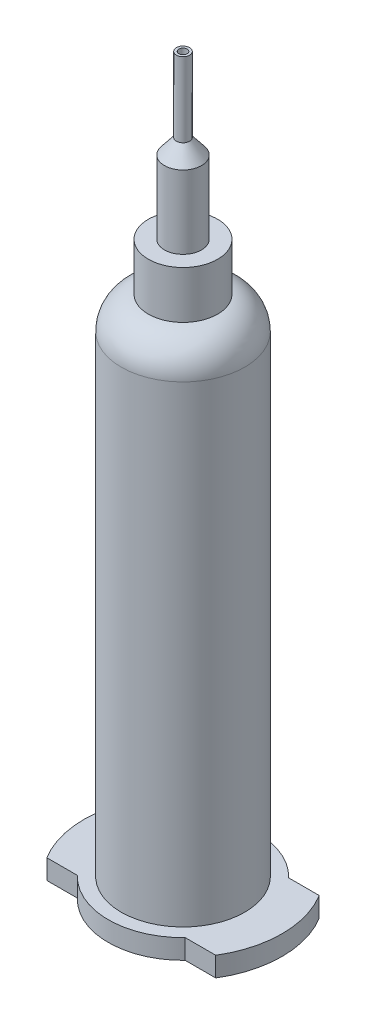
SolidWorks part; units mm, degrees
ref_plane "Front Plane" through (0, 0, 0) normal (0, 0, 1) x (1, 0, 0)
ref_plane "Top Plane" through (0, 0, 0) normal (0, 1, 0) x (1, 0, 0)
ref_plane "Right Plane" through (0, 0, 0) normal (1, 0, 0) x (0, 0, -1)
ref_axis "Axis1" through (-33.0333, 0, 0) along (1, 0, 0)
ref_axis "Axis2" through (0, 24.5224, 0) along (0, -1, 0)
ref_axis "Axis3" through (0, 0, -52.9538) along (0, 0, 1)
sketch "Sketch2" plane through (0, 0, 0) normal (0, 0, 1) x (1, 0, 0)
  line L9 (0, 54.38) -> (1, 54.38)
  line L10 (1, 54.38) -> (1, 43.03)
  line L11 (1, 43.03) -> (2.825, 40.74)
  line L12 (2.825, 40.74) -> (2.825, 29.62)
  line L13 (2.825, 29.62) -> (5.275, 29.62)
  line L14 (5.275, 29.62) -> (5.275, 22.38)
  line L15 (5.275, 22.38) -> (9.4, 22.38)
  line L16 (9.4, 22.38) -> (9.4, -54.38)
  line L17 (9.4, -54.38) -> (15.075, -54.38)
  line L18 (15.075, -54.38) -> (15.075, -57.38)
  line L19 (15.075, -57.38) -> (0, -57.38)
  line L20 (0, 54.38) -> (0, -54.38)
  line L21 (0, -54.38) -> (9.4, -54.38) construction
  line L22 (0, -57.38) -> (0, -54.38)
  point P13 (0, 0)
  dimension "D2" = 1
  dimension "D3" = 11.35
  dimension "D4" = 9.4
  dimension "D5" = 5.275
  dimension "D6" = 2.825
  dimension "D7" = 32
  dimension "D8" = 24.76
  dimension "D9" = 3
  dimension "D10" = 2.29
  dimension "D11" = 76.76
  dimension "D12" = 15.075
revolve "Revolve1" add sketch "Sketch2" angle 360 about axis through (0, 24.5224, 0) along (0, -1, 0) region at (4.5621, -13.1889, 0)
fillet "Fillet1" radius 5 1 edges at (0, 22.38, 9.4)
sketch "Sketch3" plane through (0, -54.38, 0) normal (0, 1, 0) x (1, 0, 0)
  line L0 (-12.8546, 7.875) -> (-8.2082, 7.875)
  line L1 (8.2082, 7.875) -> (12.8546, 7.875)
  line L2 (-111.883, 0) -> (111.883, 0) construction
  line L3 (-12.8546, -7.875) -> (-8.2082, -7.875)
  line L4 (8.2082, -7.875) -> (12.8546, -7.875)
  circle A0 centre (0, 0) radius 15.075 construction
  arc A1 (-8.2082, 7.875) -> (8.2082, 7.875) centre (0, 0) cw
  arc A2 (-12.8546, 7.875) -> (12.8546, 7.875) centre (0, 0) cw
  arc A3 (-8.2082, -7.875) -> (8.2082, -7.875) centre (0, 0) ccw
  arc A4 (-12.8546, -7.875) -> (12.8546, -7.875) centre (0, 0) ccw
  dimension "D2" = 11.375
  dimension "D1" = 15.75
extrude "Cut-Extrude1" cut sketch "Sketch3" against normal up to surface (3 mm away) up to face at (0, -57.38, 15.075)
sketch "Sketch4" plane through (0, -57.38, 0) normal (0, -1, 0) x (1, 0, 0)
  circle A0 centre (0, 0) radius 7.925
  dimension "D1" = 15.85
extrude "Cut-Extrude2" cut sketch "Sketch4" against normal blind 74
sketch "Sketch5" plane through (0, 54.38, 0) normal (0, 1, 0) x (1, 0, 0)
  circle A0 centre (0, 0) radius 0.6274
extrude "Cut-Extrude3" cut sketch "Sketch5" against normal blind 41
fillet "Fillet3" radius 10 1 edges at (0, 16.62, -0.6274)
ref_plane "Plane1" through (0, 16.62, 0) normal (0, 1, 0) x (1, 0, 0)
sketch "Sketch6" plane through (0, 16.62, 0) normal (0, 1, 0) x (1, 0, 0)
  circle A0 centre (0, 0) radius 7.925
  circle A1 centre (0, 0) radius 7.925 construction
extrude "Boss-Extrude2" add sketch "Sketch6" against normal blind 31 separate body
